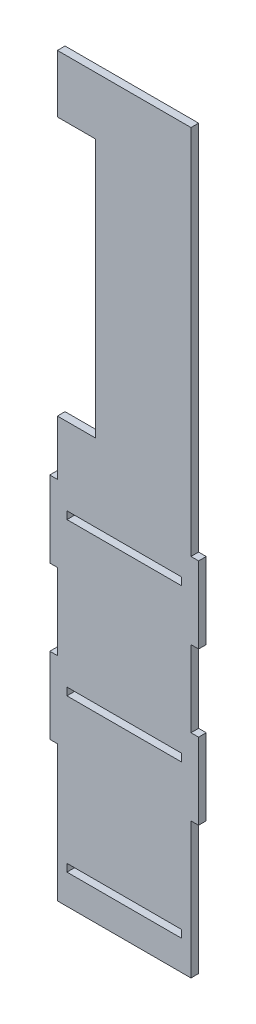
SolidWorks part; units mm, degrees
ref_plane "前视基准面" through (0, 0, 0) normal (0, 0, 1) x (1, 0, 0)
ref_plane "上视基准面" through (0, 0, 0) normal (0, 1, 0) x (1, 0, 0)
ref_plane "右视基准面" through (0, 0, 0) normal (1, 0, 0) x (0, 0, -1)
sketch "草图1" plane through (0, 0, 0) normal (0, 0, 1) x (1, 0, 0)
  line L39 (-8, 49) -> (27, 49)
  line L91 (-8, 49) -> (-8, 33.8931)
  line L92 (-8, 33.8931) -> (2, 33.8931)
  line L93 (2, 33.8931) -> (2, -33.9722)
  line L96 (-8, -48.3425) -> (-10, -48.3425)
  line L97 (-10, -48.3425) -> (-10, -68.3425)
  line L98 (-10, -68.3425) -> (-8, -68.3425)
  line L99 (-8, -68.3425) -> (-8, -88.3425)
  line L100 (-8, -88.3425) -> (-10, -88.3425)
  line L101 (-10, -88.3425) -> (-10, -108.3425)
  line L102 (-10, -108.3425) -> (-8, -108.3425)
  line L104 (-8, -108.3425) -> (-8, -144)
  line L105 (-8, -144) -> (27, -144)
  line L109 (-8, -36.9722) -> (-8, -48.3425)
  line L110 (2, -33.9722) -> (-8, -33.9722)
  line L111 (-8, -33.9722) -> (-8, -36.9722)
  line L112 (27, -48.3425) -> (29, -48.3425)
  line L113 (29, -48.3425) -> (29, -68.3425)
  line L114 (29, -68.3425) -> (27, -68.3425)
  line L115 (27, -88.3425) -> (29, -88.3425)
  line L116 (29, -88.3425) -> (29, -108.3425)
  line L117 (29, -108.3425) -> (27, -108.3425)
  line L118 (27, -144) -> (27, -108.3425)
  line L119 (27, -88.3425) -> (27, -68.3425)
  line L120 (27, -48.3425) -> (27, 49)
  line L121 (9.5, -54.2215) -> (24.5, -54.2215)
  line L135 (9.5, -54.2215) -> (-5.5, -54.2215)
  line L136 (-5.5, -54.2215) -> (-5.5, -56.2215)
  line L143 (24.5, -54.2215) -> (24.5, -56.2215)
  line L144 (24.5, -56.2215) -> (-5.5, -56.2215)
  line L146 (24.5, -94.2215) -> (-5.5, -94.2215)
  line L147 (-5.5, -94.2215) -> (-5.5, -96.2215)
  line L148 (-5.5, -96.2215) -> (24.5, -96.2215)
  line L149 (24.5, -94.2215) -> (24.5, -96.2215)
  line L150 (24.5, -134.2215) -> (-5.5, -134.2215)
  line L151 (-5.5, -134.2215) -> (-5.5, -136.2215)
  line L152 (-5.5, -136.2215) -> (24.5, -136.2215)
  line L153 (24.5, -136.2215) -> (24.5, -134.2215)
extrude "凸台-拉伸2" add sketch "草图1" along normal blind 2
